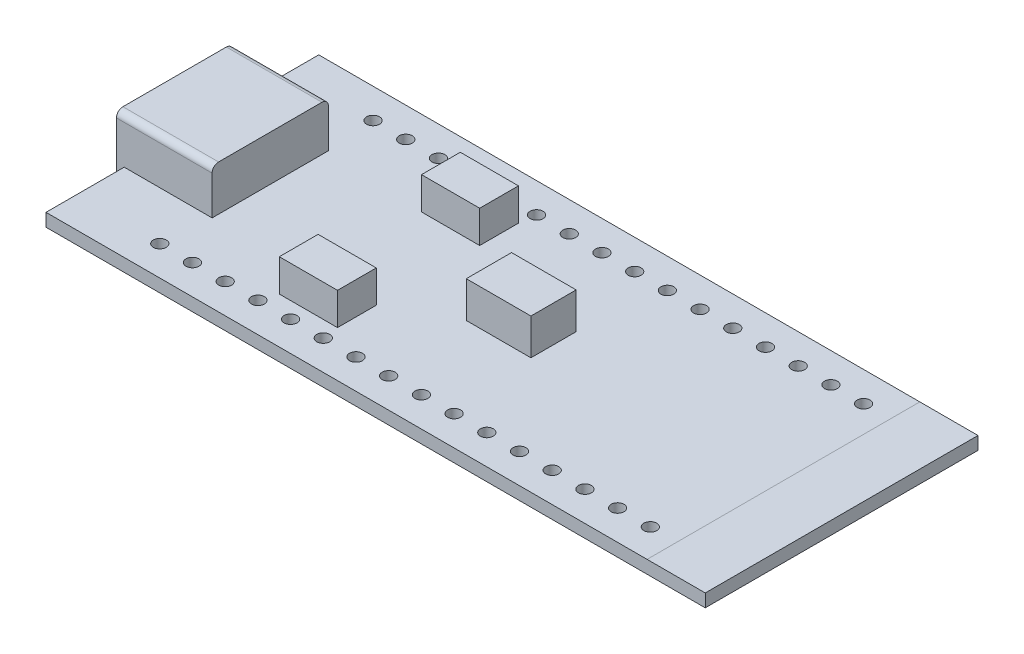
SolidWorks part; units mm, degrees
ref_plane "前视基准面" through (0, 0, 0) normal (0, 0, 1) x (1, 0, 0)
ref_plane "上视基准面" through (0, 0, 0) normal (0, 1, 0) x (1, 0, 0)
ref_plane "右视基准面" through (0, 0, 0) normal (1, 0, 0) x (0, 0, -1)
sketch "草图1" plane through (0, 0, 0) normal (0, 1, 0) x (1, 0, 0)
  line L1 (-25.5, 10.55) -> (25.5, 10.55)
  line L2 (-25.5, 10.55) -> (-25.5, -10.55)
  line L3 (-25.5, -10.55) -> (25.5, -10.55)
  line L4 (25.5, 10.55) -> (25.5, -10.55)
  line L5 (-25.5, 10.55) -> (25.5, -10.55) construction
  line L6 (-25.5, -10.55) -> (25.5, 10.55) construction
  point P0 (0, 0)
  dimension "D1" = 51
  dimension "D2" = 21.1
extrude "凸台-拉伸1" add sketch "草图1" along normal blind 1
sketch "草图2" plane through (0, 1, 0) normal (0, 1, 0) x (1, 0, 0)
  line L0 (0, 0) -> (-25.5, 0) construction
  line L1 (-26.1, 4.5) -> (-18.7, 4.5)
  line L2 (-26.1, 4.5) -> (-26.1, -4.5)
  line L3 (-26.1, -4.5) -> (-18.7, -4.5)
  line L4 (-18.7, 4.5) -> (-18.7, -4.5)
  line L5 (-25.5, 10.55) -> (-25.5, -10.55) construction
  line L6 (25.5, -10.55) -> (25.5, 10.55) construction
  dimension "D1" = 7.4
  dimension "D2" = 9
  dimension "D3" = 51.6
extrude "凸台-拉伸2" add sketch "草图2" along normal blind 4.5 from surface starting at face at (0, 0, 0)
fillet "圆角1" radius 0.5 2 edges at (-22.4, 4.5, -4.5) (-22.4, 4.5, 4.5)
sketch "草图3" plane through (0, 1, 0) normal (0, 1, 0) x (1, 0, 0)
  line L0 (21, 10.55) -> (21, -10.55)
  line L1 (25.5, 10.55) -> (-25.5, 10.55) construction
  line L2 (-25.5, -10.55) -> (25.5, -10.55) construction
  line L3 (21, -10.55) -> (25.5, -10.55)
  line L4 (25.5, -10.55) -> (25.5, 10.55)
  line L5 (25.5, -10.55) -> (25.5, 10.55) construction
  line L6 (25.5, 10.55) -> (21, 10.55)
  dimension "D1" = 4.5
wrap "包覆1" sketch "草图3" wrap type scribe source sketch "草图3" face at (-11.05, 1, 0)
sketch "草图4" plane through (0, 1, 0) normal (0, 1, 0) x (1, 0, 0)
  line L0 (0, 0) -> (-16.2813, 0) construction
  line L1 (-11, -4) -> (-6.5, -4)
  line L2 (-11, -4) -> (-11, -7)
  line L3 (-11, -7) -> (-6.5, -7)
  line L4 (-6.5, -4) -> (-6.5, -7)
  line L5 (-6.5, 4) -> (-6.5, 7)
  line L10 (-11, 7) -> (-6.5, 7)
  line L11 (-11, 4) -> (-11, 7)
  line L12 (-11, 4) -> (-6.5, 4)
  line L13 (-25.5, 10.55) -> (-25.5, 4.5) construction
  dimension "D1" = 4.5
  dimension "D2" = 3
  dimension "D3" = 14
  dimension "D4" = 19
extrude "凸台-拉伸3" add sketch "草图4" along normal blind 3.5 from surface starting at face at (-12.9, 0, 0)
sketch "草图5" plane through (0, 1, 0) normal (0, 1, 0) x (1, 0, 0)
  line L1 (-1.9968, 1.96) -> (3.0032, 1.96)
  line L2 (-1.9968, 1.96) -> (-1.9968, -1.54)
  line L3 (-1.9968, -1.54) -> (3.0032, -1.54)
  line L4 (3.0032, 1.96) -> (3.0032, -1.54)
  dimension "D1" = 5
  dimension "D2" = 3.5
extrude "凸台-拉伸4" add sketch "草图5" along normal blind 2.8
sketch "草图6" plane through (0, 0, 0) normal (0, -1, 0) x (1, 0, 0)
  line L0 (-19, 8.75) -> (-11.417, 8.75) construction
  line L1 (-25.5, 10.55) -> (25.5, 10.55) construction
  line L2 (-19.5, 8.25) -> (-19.5, 10.4693) construction
  line L4 (-25.5, 4.5) -> (-25.5, 10.55) construction
  line L6 (0, 0) -> (-26.1, 0) construction
  line L7 (-26.1, -4.5) -> (-26.1, 4.5) construction
  line L8 (-19.5, -8.25) -> (-19.5, -10.4693) construction
  line L9 (-19, -8.75) -> (-11.417, -8.75) construction
  circle A0 centre (-19, 8.25) radius 0.5
  circle A16 centre (-16.47, 8.25) radius 0.5
  circle A17 centre (-13.94, 8.25) radius 0.5
  circle A18 centre (-11.41, 8.25) radius 0.5
  circle A19 centre (-8.88, 8.25) radius 0.5
  circle A20 centre (-6.35, 8.25) radius 0.5
  circle A21 centre (-3.82, 8.25) radius 0.5
  circle A22 centre (-1.29, 8.25) radius 0.5
  circle A23 centre (1.24, 8.25) radius 0.5
  circle A24 centre (3.77, 8.25) radius 0.5
  circle A25 centre (6.3, 8.25) radius 0.5
  circle A26 centre (8.83, 8.25) radius 0.5
  circle A27 centre (11.36, 8.25) radius 0.5
  circle A28 centre (13.89, 8.25) radius 0.5
  circle A29 centre (16.42, 8.25) radius 0.5
  circle A30 centre (18.95, 8.25) radius 0.5
  circle A31 centre (18.95, -8.25) radius 0.5
  circle A32 centre (16.42, -8.25) radius 0.5
  circle A33 centre (13.89, -8.25) radius 0.5
  circle A34 centre (11.36, -8.25) radius 0.5
  circle A35 centre (8.83, -8.25) radius 0.5
  circle A36 centre (6.3, -8.25) radius 0.5
  circle A37 centre (3.77, -8.25) radius 0.5
  circle A38 centre (1.24, -8.25) radius 0.5
  circle A39 centre (-1.29, -8.25) radius 0.5
  circle A40 centre (-3.82, -8.25) radius 0.5
  circle A41 centre (-6.35, -8.25) radius 0.5
  circle A42 centre (-8.88, -8.25) radius 0.5
  circle A43 centre (-11.41, -8.25) radius 0.5
  circle A44 centre (-13.94, -8.25) radius 0.5
  circle A45 centre (-16.47, -8.25) radius 0.5
  circle A46 centre (-19, -8.25) radius 0.5
  point P4 (-15.2085, 8.75)
  dimension "D1" = 1
  dimension "D2" = 1.8
  dimension "D3" = 6.5
  dimension "D5" = 2.53
  dimension "D4" = 16
extrude "切除-拉伸1" cut sketch "草图6" against normal up to next (1 mm away)
